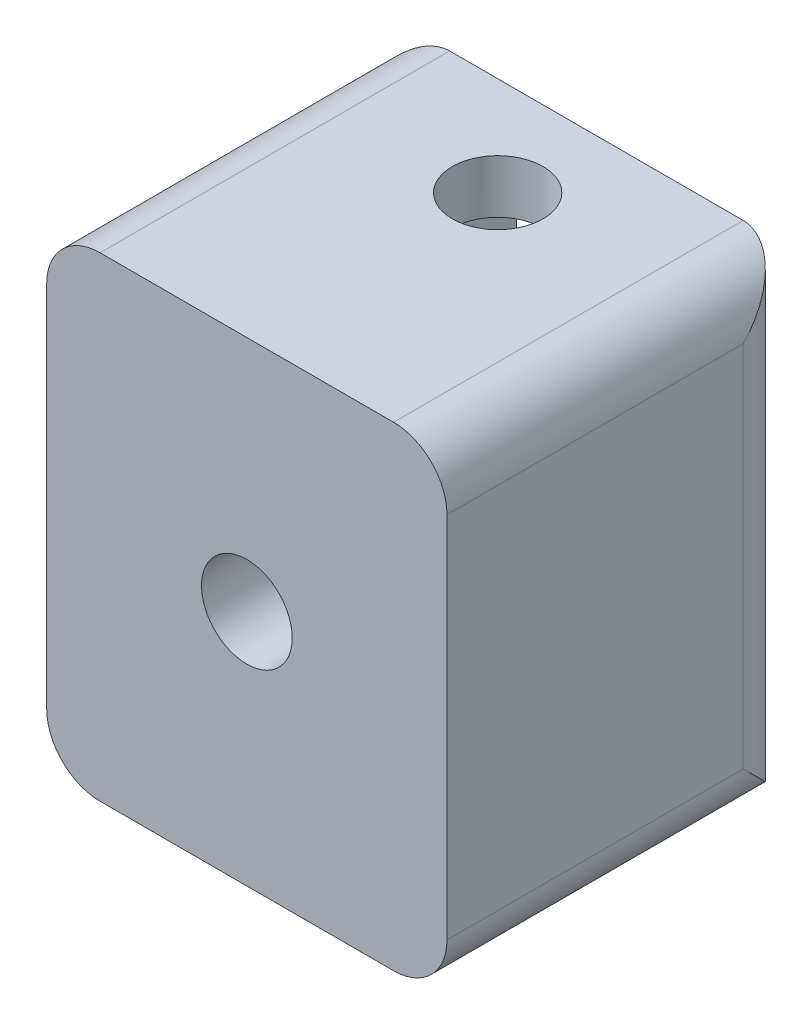
SolidWorks part; units mm, degrees
ref_plane "前视基准面" through (0, 0, 0) normal (0, 0, 1) x (1, 0, 0)
ref_plane "上视基准面" through (0, 0, 0) normal (0, 1, 0) x (1, 0, 0)
ref_plane "右视基准面" through (0, 0, 0) normal (1, 0, 0) x (0, 0, -1)
sketch "草图1" plane through (0, 0, 0) normal (0, 0, 1) x (1, 0, 0)
  line L0 (-1000.2525, 0) -> (48999.7475, 0) construction
  line L1 (-7.5, -8.9) -> (7.5, -8.9)
  line L2 (-7.5, -8.9) -> (-7.5, 8.9)
  line L3 (-7.5, 8.9) -> (7.5, 8.9)
  line L4 (7.5, -8.9) -> (7.5, 8.9)
  line L5 (-7.5, -8.9) -> (7.5, 8.9) construction
  line L6 (-7.5, 8.9) -> (7.5, -8.9) construction
  line L7 (-3, 6.9) -> (3, 6.9)
  line L8 (-3, 6.9) -> (-3, 4)
  line L9 (-3, 4) -> (3, 4)
  line L10 (3, 6.9) -> (3, 4)
  line L11 (-3, 6.9) -> (3, 4) construction
  line L12 (-3, 4) -> (3, 6.9) construction
  line L13 (-3, -4) -> (3, -6.9) construction
  line L14 (-3, -6.9) -> (3, -4) construction
  line L15 (3, -6.9) -> (3, -4)
  line L16 (-3, -4) -> (3, -4)
  line L17 (-3, -6.9) -> (-3, -4)
  line L18 (-3, -6.9) -> (3, -6.9)
  circle A0 centre (0, 0) radius 1.7
  circle A1 centre (0, 0) radius 3
  point P0 (0, 0)
  point P8 (0, 5.45)
  point P19 (0, -5.45)
  dimension "D2" = 3.4
  dimension "D8" = 6
  dimension "D1" = 15
  dimension "D3" = 6
  dimension "D4" = 2.9
  dimension "D5" = 2
  dimension "D6" = 4
  dimension "D7" = 17.8
extrude "凸台-拉伸1" add sketch "草图1" along normal blind 3.2 contours L1 L4 L3 L2 A1 L18 L17 L16 L15 L7 L10 L9 L8 | A1 A0 | L10 L7 L8 L9 | L17 L18 L15 L16 region at (-7.2672, 0, 0) region at (0, 5.45, 0) region at (0, -5.45, 0) region at (-2.9151, 0, 0)
extrude "凸台-拉伸2" add sketch "草图1<3>" against normal blind 2.2 contours L1 L4 L3 L2 A1 L18 L17 L16 L15 L7 L10 L9 L8 | L10 L7 L8 L9 | L17 L18 L15 L16 region at (-7.2672, 0, 0) region at (0, 5.45, 0) region at (0, -5.45, 0)
sketch "草图1<3>" plane through (0, 0, 0) normal (0, 0, 1) x (1, 0, 0) same geometry as "草图1"
extrude "凸台-拉伸3" add sketch "草图1<4>" against normal blind 7.7 from surface contours L1 L4 L3 L2 A1 L18 L17 L16 L15 L7 L10 L9 L8 region at (-7.2672, 0, 0) starting at face at (3, 0, -2.2)
sketch "草图1<4>" plane through (0, 0, 0) normal (0, 0, 1) x (1, 0, 0) same geometry as "草图1"
sketch "草图2" plane through (0, 0, 0) normal (0, 1, 0) x (1, 0, 0)
  circle A0 centre (0, 6.2) radius 1.7
  dimension "D1" = 3.4
  dimension "D2" = 3.7
extrude "切除-拉伸1" cut sketch "草图2" against normal through all and the other way through all
fillet "圆角1" radius 2 6 edges at (7.5, 0, -9.9) (-7.5, 0, -9.9) (-7.5, -8.9, -3.35) (7.5, -8.9, -3.35) (7.5, 8.9, -3.35) (-7.5, 8.9, -3.35)
